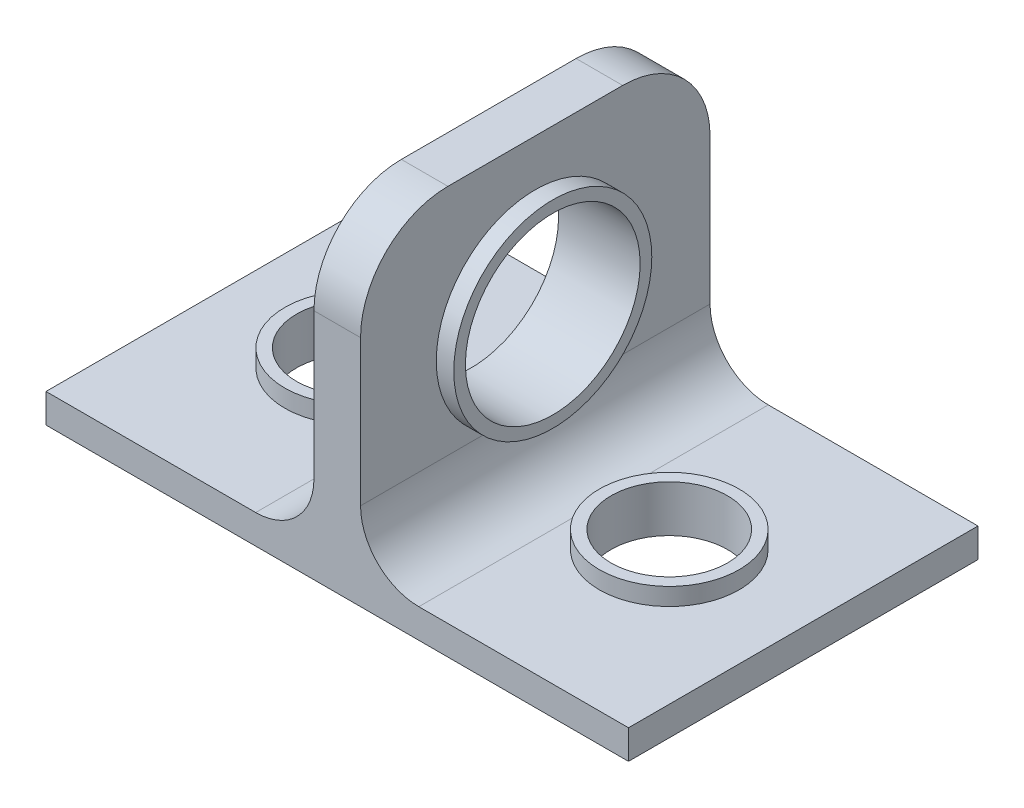
SolidWorks part; units mm, degrees
ref_plane "Front Plane" through (0, 0, 0) normal (0, 0, 1) x (1, 0, 0)
ref_plane "Top Plane" through (0, 0, 0) normal (0, 1, 0) x (1, 0, 0)
ref_plane "Right Plane" through (0, 0, 0) normal (1, 0, 0) x (0, 0, -1)
sketch "Sketch2" plane through (0, 0, 0) normal (0, 1, 0) x (1, 0, 0)
  line L0 (0, 30) -> (0, -30) construction
  line L1 (-50, 30) -> (50, 30)
  line L2 (-50, 30) -> (-50, -30)
  line L3 (-50, -30) -> (50, -30)
  line L4 (50, 30) -> (50, -30)
  line L5 (-50, 30) -> (50, -30) construction
  line L6 (-50, -30) -> (50, 30) construction
  circle A0 centre (-27, 0) radius 10
  circle A1 centre (27, 0) radius 10
  point P0 (0, 0)
  point P10 (0, 0)
  dimension "D3" = 54
  dimension "D1" = 100
  dimension "D2" = 60
extrude "Boss-Extrude1" add sketch "Sketch2" along normal blind 5
sketch "Sketch3" plane through (0, 5, 0) normal (0, 1, 0) x (1, 0, 0)
  circle A0 centre (-27, 0) radius 12
  circle A1 centre (-27, 0) radius 10
  circle A2 centre (27, 0) radius 10
  circle A3 centre (27, 0) radius 12
extrude "Boss-Extrude2" add sketch "Sketch3" along normal blind 3
sketch "Sketch4" plane through (0, 5, 0) normal (0, 1, 0) x (1, 0, 0)
  line L0 (-50, -30) -> (50, -30) construction
  line L1 (-4, 30) -> (4, 30)
  line L2 (-4, 30) -> (-4, -30)
  line L3 (-4, -30) -> (4, -30)
  line L4 (4, 30) -> (4, -30)
  line L5 (-4, 30) -> (4, -30) construction
  line L6 (-4, -30) -> (4, 30) construction
  line L7 (0, 35.6276) -> (0, -39.6339) construction
  point P0 (0, 0)
  dimension "D1" = 8
extrude "Boss-Extrude3" add sketch "Sketch4" along normal blind 50
sketch "Sketch5" plane through (-4, 0, 0) normal (-1, 0, 0) x (0, 0, 1)
  line L0 (-30, 30) -> (30, 30) construction
  line L1 (-30, 55) -> (-30, 5) construction
  line L2 (30, 55) -> (30, 5) construction
  circle A0 centre (0, 30) radius 17
extrude "Boss-Extrude4" add sketch "Sketch5" along normal blind 3 and the other way blind 11
sketch "Sketch6" plane through (-7, 0, 0) normal (-1, 0, 0) x (0, 0, 1)
  circle A0 centre (0, 30) radius 15
extrude "Cut-Extrude1" cut sketch "Sketch6" against normal up to surface (14 mm away) up to face at (7, 30, 17)
fillet "Fillet1" radius 15 2 edges at (0, 55, -30) (0, 55, 30)
fillet "Fillet2" radius 10 2 edges at (-4, 5, 0) (4, 5, 0)
